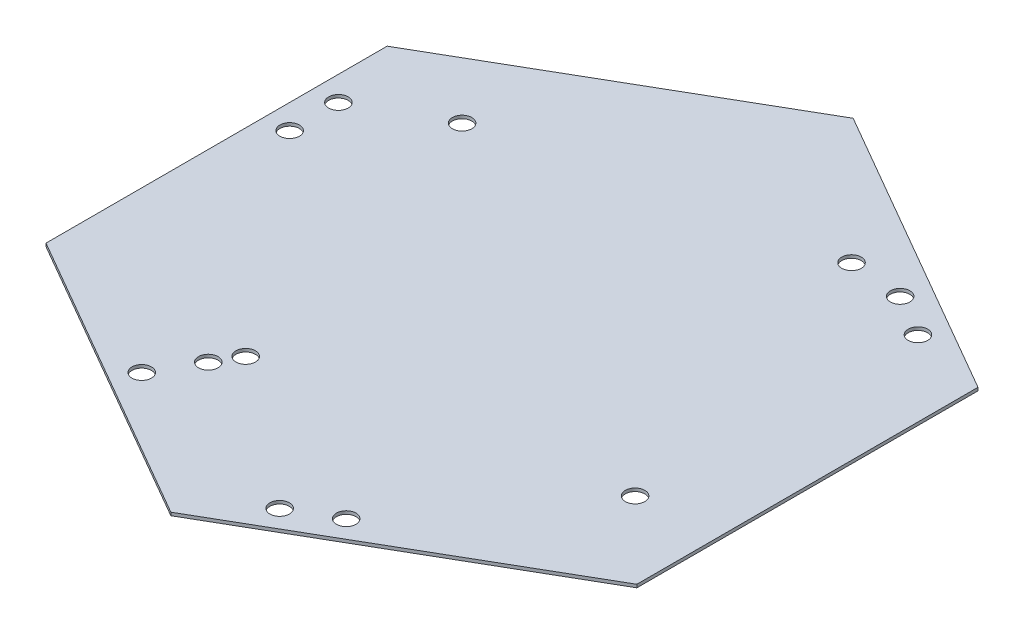
SolidWorks part; units mm, degrees
material "5052-H32"
ref_plane "Front Plane" through (0, 0, 0) normal (0, 0, 1) x (1, 0, 0)
ref_plane "Top Plane" through (0, 0, 0) normal (0, 1, 0) x (1, 0, 0)
ref_plane "Right Plane" through (0, 0, 0) normal (1, 0, 0) x (0, 0, -1)
sketch "Sketch1" plane through (0, 0, 0) normal (0, 1, 0) x (1, 0, 0)
  line L0 (13.3228, -73.8757) -> (24.3213, -67.5257) construction
  line L1 (0, 88.9) -> (-76.9897, 44.45)
  line L2 (-76.9897, 44.45) -> (-76.9897, -44.45)
  line L3 (-76.9897, -44.45) -> (0, -88.9)
  line L4 (0, -88.9) -> (76.9897, -44.45)
  line L5 (76.9897, -44.45) -> (76.9897, 44.45)
  line L6 (76.9897, 44.45) -> (0, 88.9)
  line L7 (24.3213, -67.5257) -> (27.4963, -73.025) construction
  line L8 (-70.6397, 12.7) -> (-76.9897, 12.7) construction
  line L9 (-70.6397, 25.4) -> (-70.6397, 12.7) construction
  line L10 (46.3184, 54.8257) -> (49.4934, 60.325) construction
  line L11 (57.3169, 48.4757) -> (46.3184, 54.8257) construction
  line L12 (13.3228, -73.8757) -> (16.4978, -79.375) construction
  circle A0 centre (0, 0) radius 76.9897 construction
  circle A1 centre (13.3228, -73.8757) radius 2.54
  circle A2 centre (24.3213, -67.5257) radius 2.54
  circle A7 centre (-70.6397, 12.7) radius 2.54
  circle A8 centre (-70.6397, 25.4) radius 2.54
  circle A9 centre (46.3184, 54.8257) radius 2.54
  circle A10 centre (57.3169, 48.4757) radius 2.54
  point P13 (38.4948, -66.675)
  point P28 (3.175, -1.8331)
  point P29 (0, 0)
  dimension "D2" = 5.08
  dimension "D3" = 6.35
  dimension "D4" = 12.7
  dimension "D1" = 177.8
  dimension "D5" = 12.7
extrude "Boss-Extrude1" add sketch "Sketch1" along normal blind 0.8128
sketch "Sketch2" plane through (0, 0.8128, 0) normal (0, 1, 0) x (1, 0, 0)
  line L0 (-49.8503, 36.8467) -> (56.8353, -24.7483) construction
  line L1 (27.9428, -74.7916) -> (-78.7428, -13.1966) construction
  line L2 (27.9428, -74.7916) -> (85.7278, 25.295) construction
  line L3 (85.7278, 25.295) -> (-20.9578, 86.89) construction
  line L4 (-78.7428, -13.1966) -> (-20.9578, 86.89) construction
  line L5 (-76.9897, -44.45) -> (0, -88.9) construction
  line L6 (32.385, 56.0925) -> (-25.4, -43.9941) construction
  circle A0 centre (-49.8503, 36.8467) radius 2.54
  circle A1 centre (-25.4, -43.9941) radius 2.54
  circle A2 centre (32.385, 56.0925) radius 2.54
  circle A3 centre (56.8353, -24.7483) radius 2.54
  dimension "D5" = 5.08
  dimension "D6" = 57.785
  dimension "D1" = 123.19
  dimension "D2" = 115.57
  dimension "D3" = 61.595
  dimension "D4" = 50.8
  dimension "D7" = 61.595
extrude "Cut-Extrude1" cut sketch "Sketch2" against normal through all
sketch "Sketch3" plane through (0, 0.8128, 0) normal (0, 1, 0) x (1, 0, 0)
  line L0 (-35.3198, -61.1757) -> (-38.4948, -66.675) construction
  line L2 (-76.9897, -44.45) -> (0, -88.9) construction
  line L5 (-28.9698, -50.1772) -> (-35.3198, -61.1757) construction
  circle A2 centre (-35.3198, -61.1757) radius 2.54
  circle A3 centre (-28.9698, -50.1772) radius 2.54
  point P0 (-38.4948, -66.675)
  dimension "D1" = 5.08
  dimension "D2" = 6.35
  dimension "D4" = 12.7
extrude "Cut-Extrude2" cut sketch "Sketch3" against normal through all
